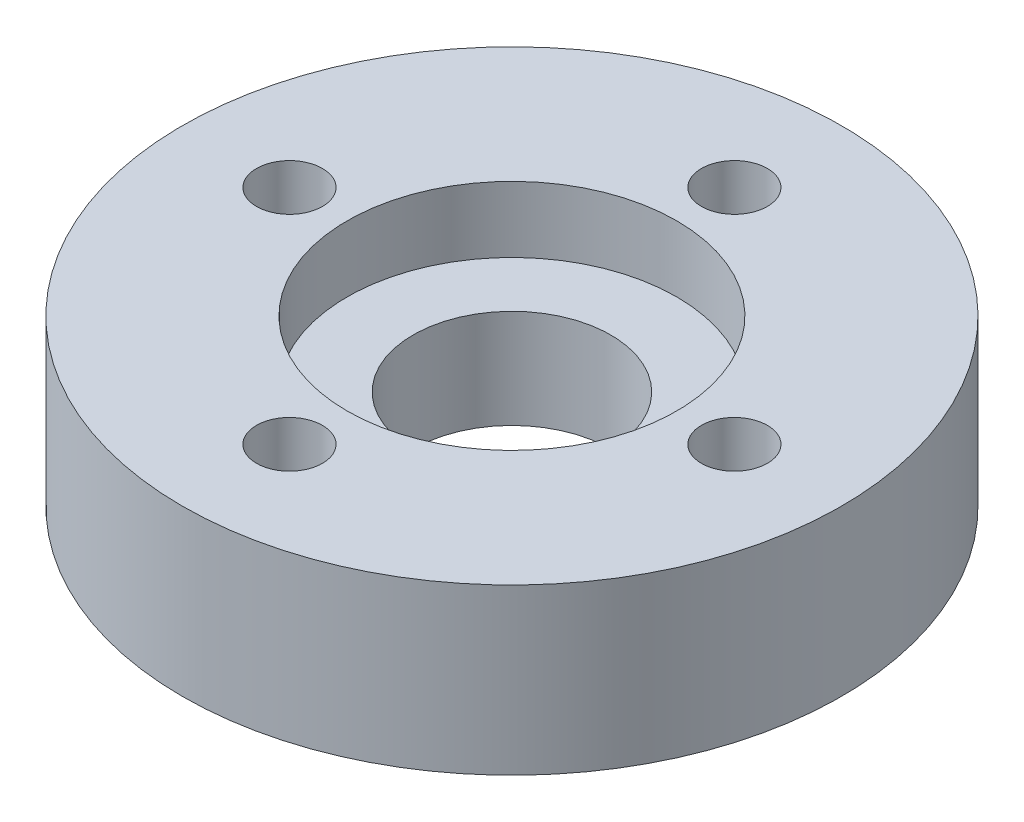
SolidWorks part; units mm, degrees
ref_plane "Front Plane" through (0, 0, 0) normal (0, 0, 1) x (1, 0, 0)
ref_plane "Top Plane" through (0, 0, 0) normal (0, 1, 0) x (1, 0, 0)
ref_plane "Right Plane" through (0, 0, 0) normal (1, 0, 0) x (0, 0, -1)
sketch "Sketch1" plane through (0, 0, 0) normal (0, 1, 0) x (1, 0, 0)
  line L0 (0, 0) -> (-6.75, 0) construction
  line L1 (0, 0) -> (0, 6.75) construction
  line L2 (0, 0) -> (0, -6.75) construction
  line L3 (0, 0) -> (6.75, 0) construction
  line L4 (-6.75, 0) -> (-8.25, 0) construction
  line L6 (-6.75, -1.7321) -> (-5.25, -0.866)
  line L7 (-5.25, -0.866) -> (-5.25, 0.866)
  line L8 (-5.25, 0.866) -> (-6.75, 1.7321)
  line L9 (-6.75, 1.7321) -> (-8.25, 0.866)
  line L10 (-8.25, 0.866) -> (-8.25, -0.866)
  line L11 (-8.25, -0.866) -> (-6.75, -1.7321)
  line L12 (1.7321, 6.75) -> (0.866, 8.25)
  line L13 (0.866, 8.25) -> (-0.866, 8.25)
  line L14 (-0.866, 8.25) -> (-1.7321, 6.75)
  line L15 (-1.7321, 6.75) -> (-0.866, 5.25)
  line L16 (-0.866, 5.25) -> (0.866, 5.25)
  line L17 (0.866, 5.25) -> (1.7321, 6.75)
  line L18 (8.2428, -0.4954) -> (7.9255, 1.0451)
  line L19 (7.9255, 1.0451) -> (6.4326, 1.5405)
  line L20 (6.4326, 1.5405) -> (5.2572, 0.4954)
  line L21 (5.2572, 0.4954) -> (5.5745, -1.0451)
  line L22 (5.5745, -1.0451) -> (7.0674, -1.5405)
  line L23 (7.0674, -1.5405) -> (8.2428, -0.4954)
  line L24 (1.7321, -6.75) -> (0.866, -5.25)
  line L25 (0.866, -5.25) -> (-0.866, -5.25)
  line L26 (-0.866, -5.25) -> (-1.7321, -6.75)
  line L27 (-1.7321, -6.75) -> (-0.866, -8.25)
  line L28 (-0.866, -8.25) -> (0.866, -8.25)
  line L29 (0.866, -8.25) -> (1.7321, -6.75)
  circle A0 centre (0, 0) radius 3
  circle A1 centre (0, 0) radius 5
  circle A2 centre (-6.75, 0) radius 1
  circle A3 centre (0, -6.75) radius 1
  circle A4 centre (6.75, 0) radius 1
  circle A5 centre (0, 6.75) radius 1
  circle A6 centre (-6.75, 0) radius 1.5 construction
  circle A7 centre (0, 6.75) radius 1.5 construction
  circle A8 centre (6.75, 0) radius 1.3622 construction
  circle A9 centre (0, -6.75) radius 1.5 construction
  circle A10 centre (0, 0) radius 10
extrude "Boss-Extrude1" add sketch "Sketch1" along normal blind 3 contours A1 A0 region at (-4.8586, 0, 0)
extrude "Boss-Extrude2" add sketch "Sketch1<3>" along normal blind 5 contours A10 L11 L10 L9 L8 L7 L6 L17 L16 L15 L14 L13 L12 L23 L22 L21 L20 L19 L18 L29 L28 L27 L26 L25 L24 A1 region at (-9.7172, 0, 0)
sketch "Sketch1<3>" plane through (0, 0, 0) normal (0, 1, 0) x (1, 0, 0) same geometry as "Sketch1"
extrude "Boss-Extrude3" add sketch "Sketch1<4>" along normal blind 2 from offset 3 contours L28 L29 L24 L25 L26 L27 A3 | L22 L23 L18 L19 L20 L21 A4 | L16 L17 L12 L13 L14 L15 A5 | L10 L11 L6 L7 L8 L9 A2 region at (-7.4771, 0, 1.2594) region at (1.2594, 0, -6.0229) region at (7.6266, 0, 0.9859) region at (1.2594, 0, 7.4771)
sketch "Sketch1<4>" plane through (0, 0, 0) normal (0, 1, 0) x (1, 0, 0) same geometry as "Sketch1"
